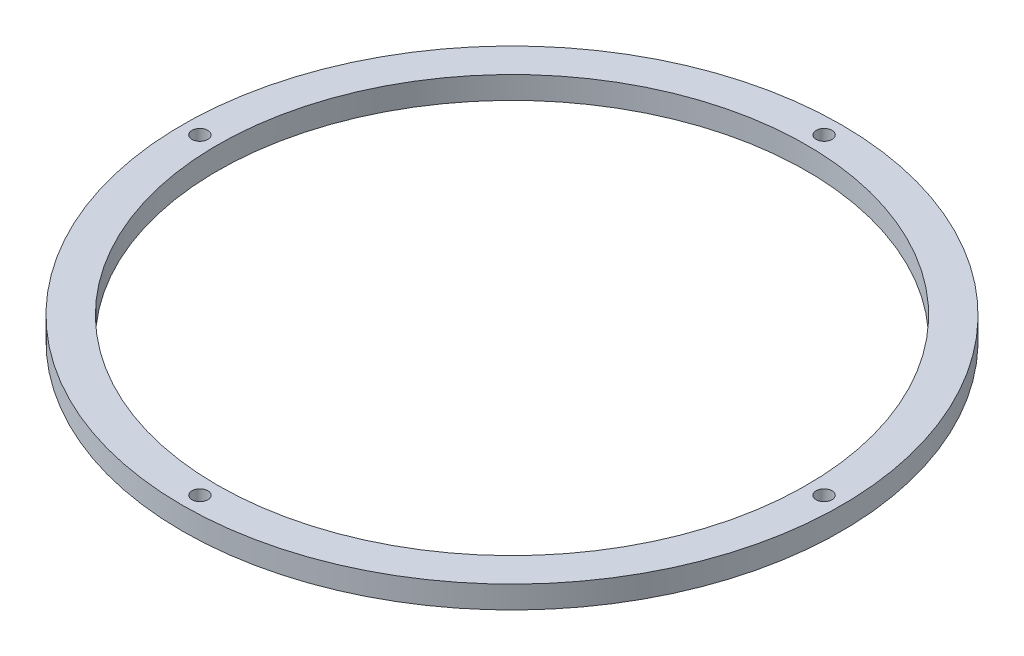
SolidWorks part; units mm, degrees
ref_plane "Front Plane" through (0, 0, 0) normal (0, 0, 1) x (1, 0, 0)
ref_plane "Top Plane" through (0, 0, 0) normal (0, 1, 0) x (1, 0, 0)
ref_plane "Right Plane" through (0, 0, 0) normal (1, 0, 0) x (0, 0, -1)
sketch "Sketch1" plane through (0, 0, 0) normal (0, 1, 0) x (1, 0, 0)
  circle A0 centre (0, 0) radius 125
  circle A1 centre (0, 0) radius 111.75
  dimension "D1" = 250
  dimension "D2" = 223.5
extrude "Boss-Extrude1" add sketch "Sketch1" along normal blind 8.5
sketch "Sketch2" plane through (0, 8.5, 0) normal (0, 1, 0) x (1, 0, 0)
  circle A0 centre (0, 118.375) radius 3
  circle A1 centre (118.375, 0) radius 3
  circle A2 centre (0, -118.375) radius 3
  circle A3 centre (-118.375, 0) radius 3
  circle A4 centre (0, 0) radius 118.375 construction
  point P11 (0, 0)
  point P12 (0, 0)
  point P13 (0, 0)
  dimension "D1" = 6
  dimension "D2" = 6
  dimension "D3" = 6
  dimension "D4" = 6
  dimension "D5" = 236.75
extrude "Cut-Extrude1" cut sketch "Sketch2" against normal through all contours A2 | A3 | A1 | A0
